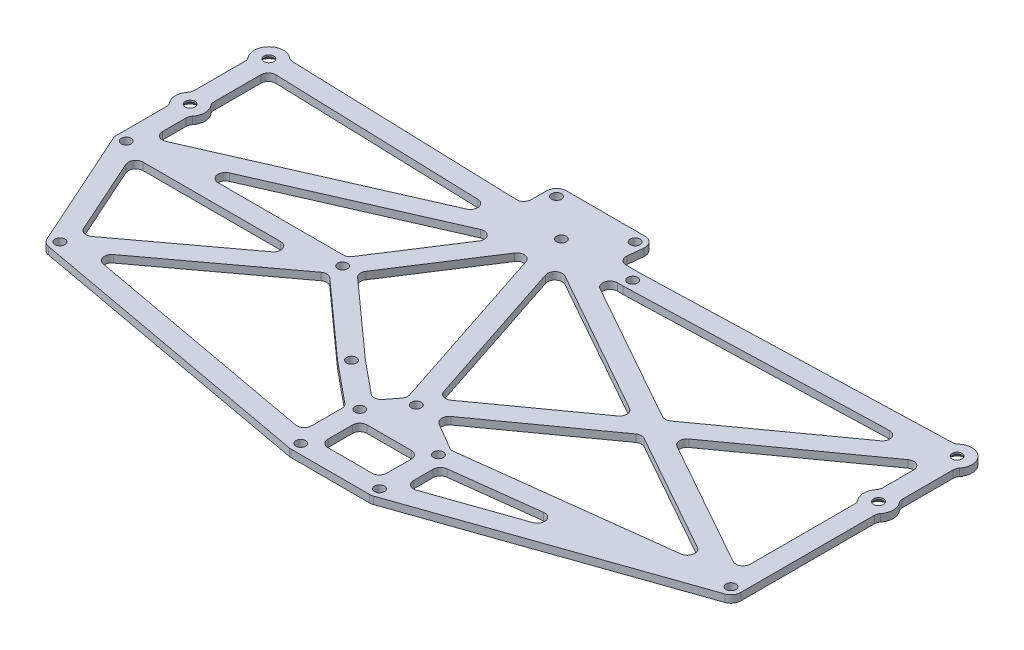
SolidWorks part; units mm, degrees
material "PC High Viscosity"
ref_plane "Front Plane" through (0, 0, 0) normal (0, 0, 1) x (1, 0, 0)
ref_plane "Top Plane" through (0, 0, 0) normal (0, 1, 0) x (1, 0, 0)
ref_plane "Right Plane" through (0, 0, 0) normal (1, 0, 0) x (0, 0, -1)
sketch "Sketch1" plane through (0, 0, 0) normal (0, 1, 0) x (1, 0, 0)
  line L0 (-148, 146) -> (-148, 0) construction
  line L1 (0, 0) -> (-296, 0)
  line L2 (0, 0) -> (0, 146)
  line L3 (0, 146) -> (-296, 146)
  line L4 (-296, 0) -> (-296, 146)
  circle A0 centre (-288, 108) radius 2
  circle A1 centre (-288, 140) radius 2
  circle A2 centre (-8, 140) radius 2
  circle A3 centre (-8, 108) radius 2
  dimension "D3" = 108
  dimension "D5" = 4
  dimension "D6" = 8
  dimension "D1" = 296
  dimension "D2" = 146
  dimension "D4" = 32
extrude "Boss-Extrude1" add sketch "Sketch1" along normal blind 3
chamfer "Chamfer1" distance 2.3 angle 45 4 edges at (-288, 0, -138) (-288, 0, -106) (-8, 0, -142) (-8, 0, -110)
sketch "Sketch2" plane through (0, 3, 0) normal (0, 1, 0) x (1, 0, 0)
  line L0 (0, 146) -> (-296, 146) construction
  line L2 (0, 0) -> (0, 146) construction
  line L3 (-296, 146) -> (-296, 0) construction
  line L4 (-296, 0) -> (0, 0) construction
  circle A0 centre (-136, 136) radius 2
  circle A1 centre (-136, 48) radius 2
  circle A2 centre (-288, 108) radius 2 construction
  circle A3 centre (-8, 48) radius 2
  circle A4 centre (-165, 136) radius 2
  circle A5 centre (-165, 50.61) radius 2
  circle A6 centre (-146, 35) radius 2
  circle A7 centre (-114, 35) radius 2
  circle A8 centre (-146, 11) radius 2
  circle A9 centre (-114, 11) radius 2
  circle A10 centre (-288, 82) radius 2
  circle A12 centre (-200, 82) radius 2
  circle A13 centre (-266, 33) radius 2
  dimension "D1" = 88
  dimension "D2" = 10
  dimension "D3" = 136
  dimension "D4" = 128
  dimension "D5" = 85.39
  dimension "D6" = 29
  dimension "D7" = 32
  dimension "D8" = 24
  dimension "D9" = 13
  dimension "D10" = 10
  dimension "D11" = 88
  dimension "D12" = 8
  dimension "D13" = 82
  dimension "D14" = 30
  dimension "D15" = 33
extrude "Cut-Extrude2" cut sketch "Sketch2" against normal blind 3
sketch "Sketch5" plane through (0, 0, 0) normal (0, -1, 0) x (1, 0, 0)
  line L0 (0, -146) -> (-296, -146) construction
  line L1 (-186, -146) -> (-144, -146)
  line L2 (-186, -146) -> (-186, -154)
  line L3 (-186, -154) -> (-144, -154)
  line L4 (-144, -146) -> (-144, -154)
  line L5 (-181, -150) -> (-149, -150) construction
  circle A0 centre (-181, -150) radius 2
  circle A1 centre (-149, -150) radius 2
  circle A2 centre (-165, -136) radius 2 construction
  point P7 (-165, -154)
  point P14 (-165, -150)
  point P15 (-186, -150)
  dimension "D1" = 32
  dimension "D3" = 5
  dimension "D2" = 8
  dimension "D4" = 110
extrude "Boss-Extrude2" add sketch "Sketch5" against normal through all
fillet "Fillet1" radius 4 4 edges at (-144, 1.5, -146) (-144, 1.5, -154) (-186, 1.5, -154) (-186, 1.5, -146)
sketch "Sketch6" plane through (0, 0, 0) normal (0, -1, 0) x (1, 0, 0)
  line L0 (-182, -154) -> (-148, -154) construction
  line L1 (-190, -146) -> (-296, -146) construction
  line L2 (-288, -140) -> (-288, -108) construction
  line L3 (-288, -108) -> (-288, -82) construction
  line L4 (-288, -82) -> (-266, -33) construction
  line L5 (-266, -33) -> (-200, -82) construction
  line L6 (-200, -82) -> (-165, -50.61) construction
  line L7 (-165, -50.61) -> (-146, -35) construction
  line L8 (-146, -35) -> (-146, -11) construction
  line L9 (-146, -11) -> (-114, -11) construction
  line L10 (-114, -11) -> (-114, -35) construction
  line L11 (-114, -35) -> (-146, -35) construction
  line L12 (-146, -35) -> (-136, -48) construction
  line L13 (-136, -48) -> (-114, -35) construction
  line L14 (-114, -35) -> (-8, -48) construction
  line L15 (-8, -48) -> (-8, -108) construction
  line L16 (-8, -108) -> (-8, -140) construction
  line L17 (-8, -140) -> (-136, -136) construction
  line L18 (-136, -136) -> (-165, -136) construction
  line L19 (-149, -150) -> (-165, -136) construction
  line L20 (-165, -136) -> (-181, -150) construction
  line L21 (-181, -150) -> (-149, -150) construction
  line L22 (-165, -136) -> (-288, -140) construction
  line L23 (-181, -150) -> (-181, -136.5203) construction
  line L24 (-149, -150) -> (-150.5, -136) construction
  line L25 (-288, -82) -> (-200, -82) construction
  line L26 (-200, -82) -> (-165, -136) construction
  line L27 (-165, -136) -> (-8, -48) construction
  line L28 (-8, -140) -> (-136, -48) construction
  line L29 (-136, -48) -> (-165, -136) construction
  line L30 (-165, -136) -> (-288, -82) construction
  line L31 (-266, -33) -> (-146, -11) construction
  line L32 (-114, -11) -> (-8, -48) construction
  line L33 (-284.3509, -83.6384) -> (-262.3509, -34.6384)
  line L34 (-265.2787, -36.9344) -> (-145.2787, -14.9344)
  line L35 (-268.3844, -36.2116) -> (-202.3844, -85.2116)
  line L36 (-197.3293, -84.9778) -> (-162.3938, -53.6457)
  line L37 (-162.3938, -53.6457) -> (-143.4608, -38.0907)
  line L38 (-142, -35) -> (-142, -11)
  line L39 (-146, -15) -> (-114, -15)
  line L40 (-115.3182, -14.7765) -> (-9.3182, -51.7765)
  line L41 (-118, -11) -> (-118, -35)
  line L42 (-114, -31) -> (-146, -31)
  line L43 (-149.1705, -37.4388) -> (-139.1705, -50.4388)
  line L44 (-133.9651, -51.4437) -> (-111.9651, -38.4437)
  line L45 (-114.4869, -38.9703) -> (-8.4869, -51.9703)
  line L46 (-163.0442, -139.4893) -> (-6.0442, -51.4893)
  line L47 (-12, -48) -> (-12, -108)
  line L48 (-12, -108) -> (-12, -140)
  line L49 (-139.799, -46.748) -> (-168.799, -134.748)
  line L50 (-5.6655, -136.7519) -> (-133.6655, -44.7519)
  line L51 (-7.8751, -136.002) -> (-135.9375, -132)
  line L52 (-135.9375, -132) -> (-165, -132)
  line L53 (-145.0228, -149.5739) -> (-146.5228, -135.5739)
  line L54 (-146.366, -146.9897) -> (-162.366, -132.9897)
  line L55 (-181, -154) -> (-149, -154)
  line L56 (-177, -150) -> (-177, -136.5203)
  line L57 (-165.13, -132.0021) -> (-284, -135.8678)
  line L58 (-284, -135.8678) -> (-284, -108)
  line L59 (-284, -108) -> (-284, -82)
  line L60 (-167.634, -132.9897) -> (-183.634, -146.9897)
  line L61 (-203.3566, -84.1756) -> (-168.3566, -138.1756)
  line L62 (-163.392, -132.3374) -> (-286.392, -78.3374)
  line L63 (-288, -86) -> (-200, -86)
  line L64 (-291.6491, -80.3616) -> (-269.6491, -31.3616)
  line L65 (-266.7213, -29.0656) -> (-146.7213, -7.0656)
  line L66 (-263.6156, -29.7884) -> (-197.6156, -78.7884)
  line L67 (-202.6707, -79.0222) -> (-167.6062, -47.5743)
  line L68 (-167.6062, -47.5743) -> (-148.5392, -31.9093)
  line L69 (-150, -35) -> (-150, -11)
  line L70 (-146, -7) -> (-114, -7)
  line L71 (-112.6818, -7.2235) -> (-6.6818, -44.2235)
  line L72 (-110, -11) -> (-110, -35)
  line L73 (-114, -39) -> (-146, -39)
  line L74 (-142.8295, -32.5612) -> (-132.8295, -45.5612)
  line L75 (-138.0349, -44.5563) -> (-116.0349, -31.5563)
  line L76 (-113.5131, -31.0297) -> (-7.5131, -44.0297)
  line L77 (-166.9558, -132.5107) -> (-9.9558, -44.5107)
  line L78 (-4, -48) -> (-4, -108)
  line L79 (-4, -108) -> (-4, -140)
  line L80 (-132.201, -49.252) -> (-161.201, -137.252)
  line L81 (-10.3345, -143.2481) -> (-138.3345, -51.2481)
  line L82 (-8.1249, -143.998) -> (-136.0625, -140)
  line L83 (-136.0625, -140) -> (-165, -140)
  line L84 (-152.9772, -150.4261) -> (-154.4772, -136.4261)
  line L85 (-151.634, -153.0103) -> (-167.634, -139.0103)
  line L86 (-181, -146) -> (-149, -146)
  line L87 (-185, -150) -> (-185, -136.5203)
  line L88 (-164.87, -139.9979) -> (-292, -144.1322)
  line L89 (-292, -144.1322) -> (-292, -108)
  line L90 (-292, -108) -> (-292, -82)
  line L91 (-162.366, -139.0103) -> (-178.366, -153.0103)
  line L92 (-196.6434, -79.8244) -> (-161.6434, -133.8244)
  line L93 (-166.608, -139.6626) -> (-289.608, -85.6626)
  line L94 (-288, -78) -> (-200, -78)
  circle A1 centre (-165, -50.61) radius 4
  circle A2 centre (-146, -35) radius 4
  circle A5 centre (-146, -11) radius 4
  circle A6 centre (-114, -11) radius 4
  circle A7 centre (-136, -48) radius 4
  circle A8 centre (-114, -35) radius 4
  circle A9 centre (-8, -48) radius 4
  circle A10 centre (-149, -150) radius 4
  circle A11 centre (-181, -150) radius 4
  circle A12 centre (-288, -82) radius 4
  circle A13 centre (-266, -33) radius 4
  circle A14 centre (-200, -82) radius 4
  circle A15 centre (-165, -136) radius 4
  circle A16 centre (-136, -136) radius 4
  circle A17 centre (-288, -140) radius 6
  circle A18 centre (-288, -108) radius 6
  circle A19 centre (-8, -140) radius 6
  circle A20 centre (-8, -108) radius 6
  line M65 (-182, -154) -> (-148, -154)
  arc M66 (-148, -154) -> (-144, -150) centre (-148, -150) ccw
  arc M67 (-144, -150) -> (-140, -146) centre (-140, -150) cw
  line M68 (-140, -146) -> (0, -146)
  line M69 (0, -146) -> (0, 0)
  line M70 (0, 0) -> (-296, 0)
  line M71 (-296, 0) -> (-296, -146)
  line M72 (-296, -146) -> (-190, -146)
  arc M73 (-190, -146) -> (-186, -150) centre (-190, -150) cw
  arc M74 (-186, -150) -> (-182, -154) centre (-182, -150) ccw
  dimension "D1" = 4
  dimension "D2" = 4
extrude "Cut-Extrude3" cut sketch "Sketch6" against normal through all both and the other way through all contours L77 L81 L80 | L51 L81 L46 L52 | L68 L69 L34 L66 L67 | L36 L92 L49 L43 L37 | L63 L62 L61 | A18 L58 A17 L57 L93 L59 | L33 L94 L35 | A20 L79 A19 A17 L89 A18 L90 A12 L64 A13 L65 A5 L70 A6 L71 A9 L78 M68 M69 M70 M71 M72 | L42 L41 L39 L38 | L72 L76 L40 | L50 L77 L45 L44 | A20 L47 L46 L50 L48 | A19 L82 L83 L53 A10 M65 M66 M67 M68 | A17 A11 L87 L88 M72 M73 M74 M65 region at (-252.7688, 0, -65.0593) region at (-215.5776, 0, -99.6563) region at (-250.08, 0, -118.9114) region at (-295.3005, 0, -92.7639) region at (-197.4938, 0, -42.472) region at (-166.1114, 0, -81.2506) region at (-226.4081, 0, -144.174) region at (-126.4133, 0, -89.934) region at (-130, 0, -23) region at (-78.7406, 0, -57.5797) region at (-83.4412, 0, -120.0893) region at (-32.2635, 0, -91.8325) region at (-90.7027, 0, -143.8442) region at (-88.1703, 0, -29.1953) body kept at (-292, 3, -112.4721)
fillet "Fillet2" radius 3 55 edges at (-284, 1.5, -135.5279) (-4, 1.5, -135.5279) (-4, 1.5, -112.4721) (-4, 1.5, -103.5279) (-292, 1.5, -103.5279) (-292, 1.5, -112.4721) (-292, 1.5, -135.5279) (-283.4002, 1.5, -143.8525) (-185, 1.5, -140.6525) (-146.0485, 1.5, -140) (-136.0625, 1.5, -140) (-12.5949, 1.5, -143.8584) (-12, 1.5, -132.199) (-72.4814, 1.5, -88.728) (-12, 1.5, -54.8275) (-12, 1.5, -103.5279) (-12, 1.5, -112.4721) (-113.1364, 1.5, -39.1359) (-20.6114, 1.5, -50.4833) (-79.6504, 1.5, -83.5752) (-128.6911, 1.5, -48.3273) (-146.6522, 1.5, -40.7127) (-166.1853, 1.5, -126.8168) (-194.7832, 1.5, -82.6944) (-175.6201, 1.5, -126.969) (-202.1741, 1.5, -86) (-149.6827, 1.5, -132) (-80.1828, 1.5, -93.0446) (-20.9861, 1.5, -135.5922) (-142, 1.5, -15) (-118, 1.5, -15) (-118, 1.5, -31) (-142, 1.5, -31) (-212.098, 1.5, -78) (-281.8194, 1.5, -78) (-264.3891, 1.5, -39.1779) (-284, 1.5, -88.1246) (-182.7515, 1.5, -132.5752) (-284, 1.5, -112.4721) (-284, 1.5, -103.5279) (-157.9807, 1.5, -127.4801) (-133.9074, 1.5, -54.4301) (-87.3518, 1.5, -87.8919) (-200.2386, 1.5, -76.841) (-256.2258, 1.5, -35.2747) (-150, 1.5, -15.8) (-150, 1.5, -33.1095) (-110, 1.5, -16.6329) (-110, 1.5, -31.4606) (-140.462, 1.5, -48.7599)
fillet "Fillet3" radius 3 1 edges at (-283.6602, 1.5, -135.8568)
